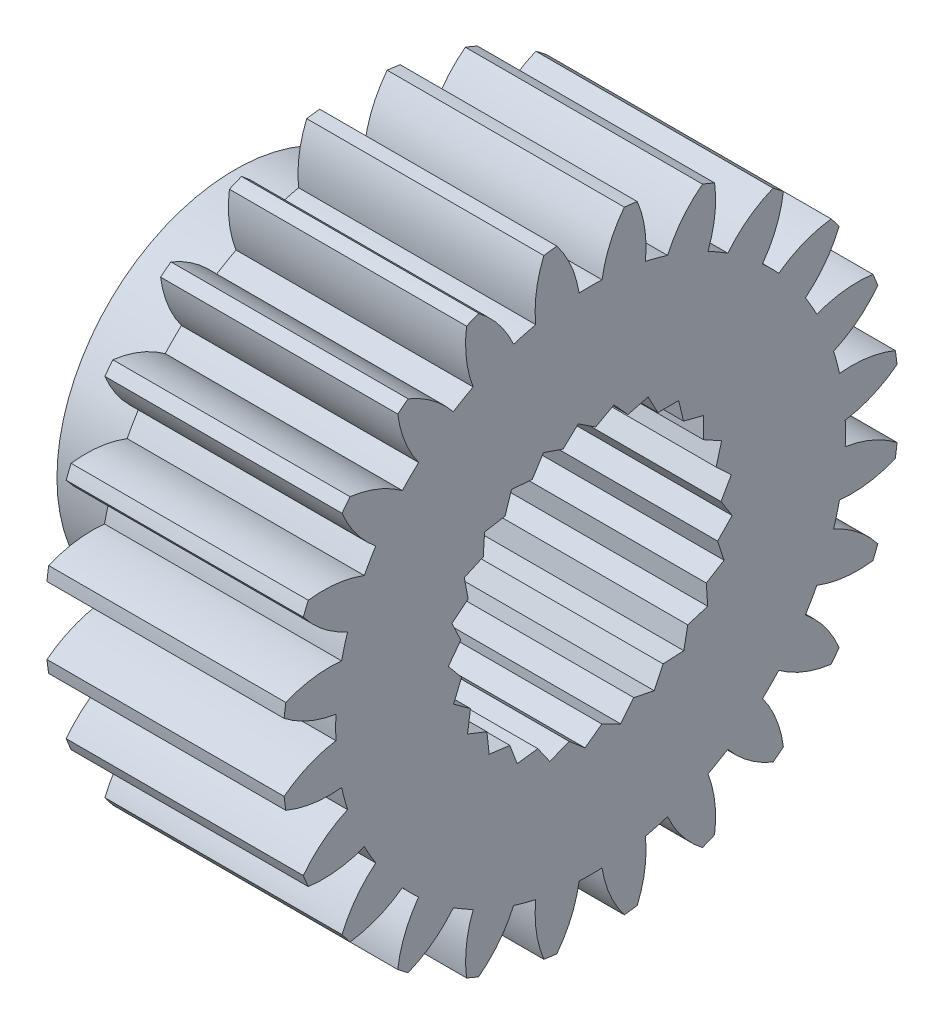
SolidWorks part; units mm, degrees
note: The reader was unsure of these and kept them because the rebuilt part matched: shared geometry of "Sketch1<3>".
ref_plane "Plane1" through (0, 0, 0) normal (0, 0, 1) x (1, 0, 0)
ref_plane "Plane2" through (0, 0, 0) normal (0, 1, 0) x (1, 0, 0)
ref_plane "Plane3" through (0, 0, 0) normal (1, 0, 0) x (0, 0, -1)
other "Configuration Table"
sketch "HoldingSke" plane through (0, 0, 0) normal (0, 1, 0) x (1, 0, 0)
  line L0 (0, 0) -> (1.8271, -0.8135)
  line L1 (-15, 0) -> (100, 0) construction
  line L2 (0, 0) -> (-2.1039, 2.3779)
  line L3 (0, 0) -> (-11.863, 4.5341)
  line L4 (0, 0) -> (7.8894, 3.5126)
  line L5 (0, 0) -> (-46.8476, -17.4728)
  line L6 (0, 0) -> (-4.1448, -2.7965)
  line L7 (-2.1039, 2.3779) -> (8.6586, 51.2059)
  line L8 (-76.2, 54.61) -> (-75.7, 54.61)
  line L9 (-71.009, 38.7566) -> (-53.1078, 45.2721)
  line L10 (-76.2, 71.12) -> (104.1128, 71.12)
  line L11 (0, 0) -> (-5, 0)
  line L12 (-76.2, 101.6) -> (-76.181, 101.6)
  line L13 (24.9733, 27.94) -> (52.9518, 28.4284)
  line L14 (24.9733, 27.94) -> (24.9743, 27.94)
  line L15 (24.9733, 27.94) -> (100.4006, 29.5858)
  line L16 (-63.627, -0.5) -> (-12.827, -0.5)
  circle A0 centre (0, 0) radius 1.5
  circle A1 centre (0, 0) radius 5.374
  circle A2 centre (0, 0) radius 37.5
  circle A3 centre (0, 0) radius 1.5
  dimension "Num_teeth" = 24
  dimension "Pitch_radius" = 180.3128
  dimension "Width" = 5
  dimension "Thickness" = 5
sketch "BasProSke" plane through (0, 0, 0) normal (0, 1, 0) x (1, 0, 0)
  line L0 (-10, 0) -> (60, 0) construction
  line L1 (0, 0) -> (0, 6.5)
  line L2 (0, 0) -> (5, 0)
  line L3 (5, 0) -> (5, 6.5)
  line L4 (5, 6.5) -> (0, 6.5)
  dimension "Thickness" = 5
  dimension "Diameter" = 13
revolve "Base-Revolve" add sketch "BasProSke" angle 360 about L0
sketch "TooCutSke" plane through (0, 0, 0) normal (1, 0, 0) x (0, 0, -1)
  line L1 (0, 0) -> (0, 107) construction
  line L2 (0, 0) -> (-0.4257, 5.9849) construction
  line L3 (0, 0) -> (-1.5635, 11.876) construction
  line L4 (-0.4257, 5.9849) -> (-0.7818, 5.938) construction
  arc A0 (0.2416, 5.3686) -> (-0.2416, 5.3686) centre (0, 0) ccw
  arc A1 (0.7297, 6.4845) -> (-0.7297, 6.4845) centre (0, 0) ccw
  circle A2 centre (0, 0) radius 6 construction
  circle A3 centre (0, 0) radius 5.6382 construction
  arc A4 (-0.2416, 5.3686) -> (-0.7297, 6.4845) centre (-2.6126, 4.9963) ccw
  arc A5 (0.7297, 6.4845) -> (0.2416, 5.3686) centre (2.6126, 4.9963) ccw
extrude "ToothCut" cut sketch "TooCutSke" along normal through all
fillet "Breaks" [suppressed] radius 0.01
fillet "RootFillets" [suppressed] radius 0.126
pattern_circular "TeethCuts" count 24 every 15 about axis through (-10, 0, 0) along (1, 0, 0) of "ToothCut", "RootFillets", "Breaks"
sketch "HubNeaOneSke" plane through (0, 0, 0) normal (-1, 0, 0) x (0, 0, 1)
  circle A0 centre (0, 0) radius 5.374
  dimension "Diameter" = 10.748
extrude "HubNearOne" [suppressed] add sketch "HubNeaOneSke" along normal blind 45.0001
sketch "HubNeaBotSke" plane through (0, 0, 0) normal (-1, 0, 0) x (0, 0, 1)
  circle A0 centre (0, 0) radius 5.374
  dimension "Diameter" = 10.748
extrude "HubNearBoth" [suppressed] add sketch "HubNeaBotSke" along normal blind 22.5
ref_plane "FarPln" through (5, 0, 0) normal (1, 0, 0) x (0, 0, -1)
sketch "HubFarSke" plane through (5, 0, 0) normal (1, 0, 0) x (0, 0, -1)
  circle A0 centre (0, 0) radius 5.374
  dimension "Diameter" = 10.748
extrude "HubFar" [suppressed] add sketch "HubFarSke" along normal blind 22.5
sketch "BorSke" plane through (0, 0, 0) normal (1, 0, 0) x (0, 0, -1)
  circle A0 centre (0, 0) radius 1.5
  dimension "Diameter" = 3
extrude "Bore" cut sketch "BorSke" along normal mid plane 100.0001
sketch "KeySke" plane through (0, 0, 0) normal (1, 0, 0) x (0, 0, -1)
  line L0 (-0.6, 0) -> (-0.6, 2)
  line L1 (-0.6, 2) -> (0.6, 2)
  line L2 (0.6, 2) -> (0.6, 0)
  line L3 (0, 0) -> (0, 34) construction
  line L4 (-0.6, 0) -> (0.6, 0)
  dimension "Width" = 1.2
extrude "Keyway" [suppressed] cut sketch "KeySke" along normal mid plane 100.0001
pattern_circular "Keyway2" [suppressed] count 2 every 90 about axis through (-10, 0, 0) along (1, 0, 0)
sketch "Sketch1" plane through (5, 0, 0) normal (1, 0, 0) x (0, 0, -1)
  line L0 (0, 0) -> (-0.6053, -3.6381) construction
  line L1 (0, 0) -> (-0.1385, -3.5322) construction
  line L2 (0, 0) -> (0.3079, -3.5524) construction
  line L3 (-0.4513, -2.7127) -> (-0.1176, -2.9977)
  line L4 (-0.1176, -2.9977) -> (0.2375, -2.7397)
  circle A0 centre (0, 0) radius 3 construction
  circle A1 centre (0, 0) radius 2.75
  dimension "D1" = 7.2
  dimension "D2" = 14.4
extrude "Cut-Extrude1" cut sketch "Sketch1" against normal through all both and the other way through all contours A1
sketch "Sketch2" plane through (0, 0, 0) normal (-1, 0, 0) x (0, 0, 1)
  circle A0 centre (0, 0) radius 3.75
  circle A1 centre (0, 0) radius 2.75
extrude "Boss-Extrude1" add sketch "Sketch2" along normal blind 2.5
extrude "Cut-Extrude2" cut sketch "Sketch1<3>" against normal through all both and the other way through all contours A1 L3 L4
sketch "Sketch1<3>" plane through (5, 0, 0) normal (1, 0, 0) x (0, 0, -1) same geometry as "Sketch1"
pattern_circular "CirPattern1" count 25 over 360 about axis through (0, 0, 0) along (1, 0, 0) of "Cut-Extrude2"
equation "' \"Module@HoldingSke\" = 6.35"
equation "' \"Num_teeth@HoldingSke\" = 12"
equation "' \"Ap@HoldingSke\" =  20"
equation "' \"Ap@HoldingSke\" = 20"
equation "' \"Width@HoldingSke\" = 0.5 * 25.4"
equation "' \"Hub_dia@HoldingSke\"= 1 * 25.4"
equation "' \"Hub_dia@HoldingSke\" = 1 * 25.4"
equation "' \"Overall_len@HoldingSke\" = 1.0 * 25.4"
equation "' \"Bore@HoldingSke\" = 0.75 * 25.4"
equation "' \"T_dim@HoldingSke\" = 0.1 * 25.4"
equation "' \"Width@KeySke\" = 0.25 * 25.4"
equation "' \"Show_teeth@HoldingSke\" = 13"
equation "' \"Backlash@HoldingSke\" = 0.009 * 25.4"
equation "' \"Addendum_fac@HoldingSke\" = 1.0"
equation "' \"Dedendum_fac@HoldingSke\" = 1.25"
equation "' \"Dedendum_add@HoldingSke\" = 0.00005 * 25.4"
equation "' \"Clearance_fac@HoldingSke\" = 0.25"
equation "\"Pitch@HoldingSke\" = 1 / \"Module@HoldingSke\""
equation "\"Overcut_dia@TooCutSke\" = (\"Num_teeth@HoldingSke\" + 2 * \"Addendum_fac@HoldingSke\") / \"Pitch@HoldingSke\" + 0.002 * 25.4"
equation "\"Pitch_dia@TooCutSke\" = \"Num_teeth@HoldingSke\" / \"Pitch@HoldingSke\""
equation "\"Base_dia@TooCutSke\" = \"Num_teeth@HoldingSke\" / \"Pitch@HoldingSke\" * cos((\"Ap@HoldingSke\"  * 3.14159265 / 180))"
equation "\"Root_dia@TooCutSke\" = (\"Num_teeth@HoldingSke\" + 2) / \"Pitch@HoldingSke\" - 2 * (\"Addendum_fac@HoldingSke\" + \"Dedendum_fac@HoldingSke\") / \"Pitch@HoldingSke\" - \"Dedendum_add@HoldingSke\" * 2"
equation "\"Half_ang@TooCutSke\" = 180 / \"Num_teeth@HoldingSke\""
equation "\"Half_CT@TooCutSke\" = \"Num_teeth@HoldingSke\" / \"Pitch@HoldingSke\" * sin((3.14159265 / 2 / \"Num_teeth@HoldingSke\")) / 2 - 7 * \"Backlash@HoldingSke\" / 4"
equation "\"Flank_rad@TooCutSke\" = \"Num_teeth@HoldingSke\" / \"Pitch@HoldingSke\" / 5"
equation "\"Radius@RootFillets\" = \"Clearance_fac@HoldingSke\" / \"Pitch@HoldingSke\" + \"Dedendum_add@HoldingSke\""
equation "\"Break_rad@Breaks\" = 0.02 / \"Pitch@HoldingSke\""
equation "\"Thickness@HoldingSke\" = \"Width@HoldingSke\""
equation "\"OAL@HoldingSke\" = \"Thickness@HoldingSke\""
equation "\"MHD@HoldingSke\" = (\"Num_teeth@HoldingSke\" + 2) / \"Pitch@HoldingSke\" - 2 * (\"Addendum_fac@HoldingSke\" + \"Dedendum_fac@HoldingSke\")  / \"Pitch@HoldingSke\" - \"Dedendum_add@HoldingSke\" * 2"
equation "\"MBD@HoldingSke\" = (\"Num_teeth@HoldingSke\" + 2) / \"Pitch@HoldingSke\" - 2 * (\"Addendum_fac@HoldingSke\" + \"Dedendum_fac@HoldingSke\")  / \"Pitch@HoldingSke\" - \"Dedendum_add@HoldingSke\" * 2 - 0.002 * 25.4"
equation "\"MHD@HoldingSke\" = ((sgn( \"MHD@HoldingSke\" - \"Hub_dia@HoldingSke\" )-1)*( \"MHD@HoldingSke\" - \"Hub_dia@HoldingSke\" ))/-2+ \"Hub_dia@HoldingSke\""
equation "\"MBD@HoldingSke\" = ((sgn( \"MBD@HoldingSke\" - \"Bore@HoldingSke\" )-1)*( \"MBD@HoldingSke\" - \"Bore@HoldingSke\" ))/-2+ \"Bore@HoldingSke\""
equation "\"OAL@HoldingSke\" = ((sgn( \"OAL@HoldingSke\" - \"Overall_len@HoldingSke\" )+1)*( \"OAL@HoldingSke\" - \"Overall_len@HoldingSke\" ))/2 + \"Overall_len@HoldingSke\" + 0.000002 * 25.4"
equation "\"Num_teeth@TeethCuts\" = int( \"Show_teeth@HoldingSke\" ) + 1"
equation "\"Num_teeth@TeethCuts\" = ((sgn( \"Num_teeth@TeethCuts\" - \"Num_teeth@HoldingSke\" )-1)*( \"Num_teeth@TeethCuts\" - \"Num_teeth@HoldingSke\" ))/-2+ \"Num_teeth@HoldingSke\""
equation "\"Num_teeth@TeethCuts\" = ((sgn( \"Num_teeth@TeethCuts\" - 2.0)+1)*( \"Num_teeth@TeethCuts\" - 2.0))/2 +2.0"
equation "\"Angle@TeethCuts\" = 360.0 / \"Num_teeth@HoldingSke\""
equation "\"Diameter@BasProSke\" = (\"Num_teeth@HoldingSke\" + 2 * \"Addendum_fac@HoldingSke\") / \"Pitch@HoldingSke\""
equation "\"Thickness@BasProSke\"  = \"Thickness@HoldingSke\""
equation "' \"Fillet_rad@BasProSke\" =  \"Thickness@HoldingSke\" * 0.05"
equation "' \"Fillet_rad@BasProSke\" = \"Thickness@HoldingSke\" * 0.05"
equation "\"MHD@HoldingSke\" = ((sgn( \"MHD@HoldingSke\" - \"Root_dia@TooCutSke\" )-1)*( \"MHD@HoldingSke\" - \"Root_dia@TooCutSke\" ))/-2+ \"Root_dia@TooCutSke\""
equation "\"Diameter@HubNeaOneSke\" = \"MHD@HoldingSke\""
equation "\"Length@HubNearOne\" = \"OAL@HoldingSke\" - \"Thickness@BasProSke\""
equation "\"Diameter@HubNeaBotSke\" = \"MHD@HoldingSke\""
equation "\"Length@HubNearBoth\" = ( \"OAL@HoldingSke\" - \"Thickness@BasProSke\" ) / 2.0"
equation "\"Thickness@FarPln\" = \"Thickness@BasProSke\""
equation "\"Diameter@HubFarSke\" = \"MHD@HoldingSke\""
equation "\"Length@HubFar\" = ( \"OAL@HoldingSke\" - \"Thickness@BasProSke\" ) / 2.0"
equation "\"Diameter@BorSke\" = \"MBD@HoldingSke\""
equation "\"D1@Bore\" = \"OAL@HoldingSke\" * 2.0"
equation "\"D1@Keyway\" = \"OAL@HoldingSke\" * 2.0"
equation "\"Offset@KeySke\" = \"T_dim@HoldingSke\" + \"MBD@HoldingSke\" / 2.0"
